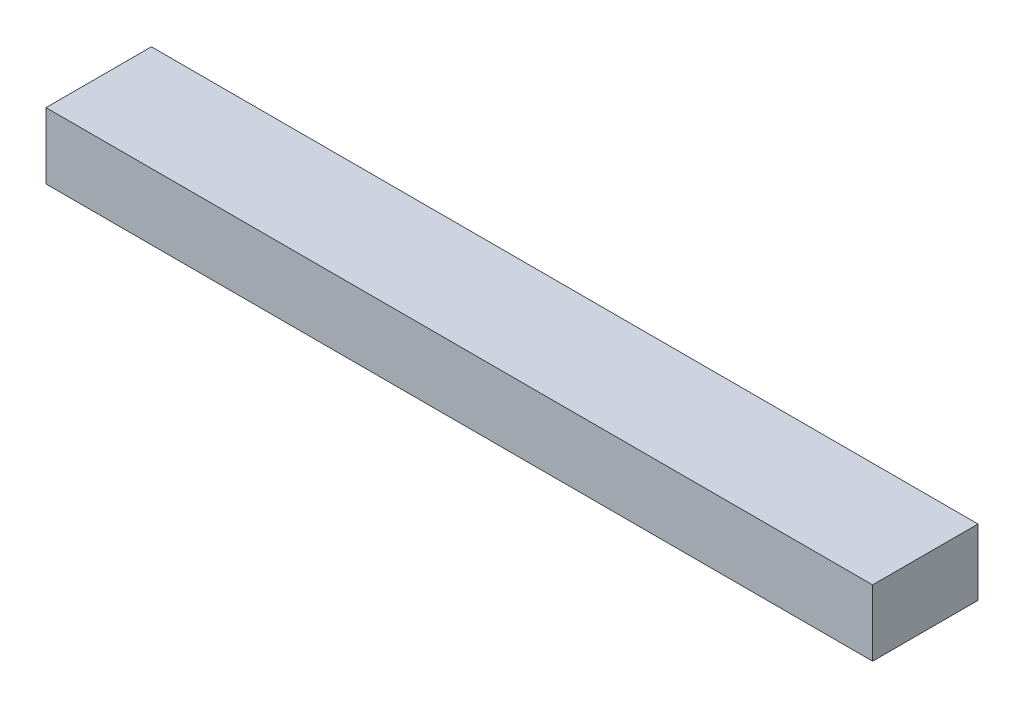
SolidWorks part; units mm, degrees
ref_plane "Front Plane" through (0, 0, 0) normal (0, 0, 1) x (1, 0, 0)
ref_plane "Top Plane" through (0, 0, 0) normal (0, 1, 0) x (1, 0, 0)
ref_plane "Right Plane" through (0, 0, 0) normal (1, 0, 0) x (0, 0, -1)
sketch "Sketch1" plane through (0, 0, 0) normal (1, 0, 0) x (0, 0, -1)
  line L1 (-6.375, -4) -> (6.375, -4)
  line L2 (-6.375, -4) -> (-6.375, 4)
  line L3 (-6.375, 4) -> (6.375, 4)
  line L4 (6.375, -4) -> (6.375, 4)
  line L5 (-6.375, -4) -> (6.375, 4) construction
  line L6 (-6.375, 4) -> (6.375, -4) construction
  point P0 (0, 0)
  dimension "D1" = 12.75
  dimension "D2" = 8
extrude "Boss-Extrude1" add sketch "Sketch1" along normal blind 100
